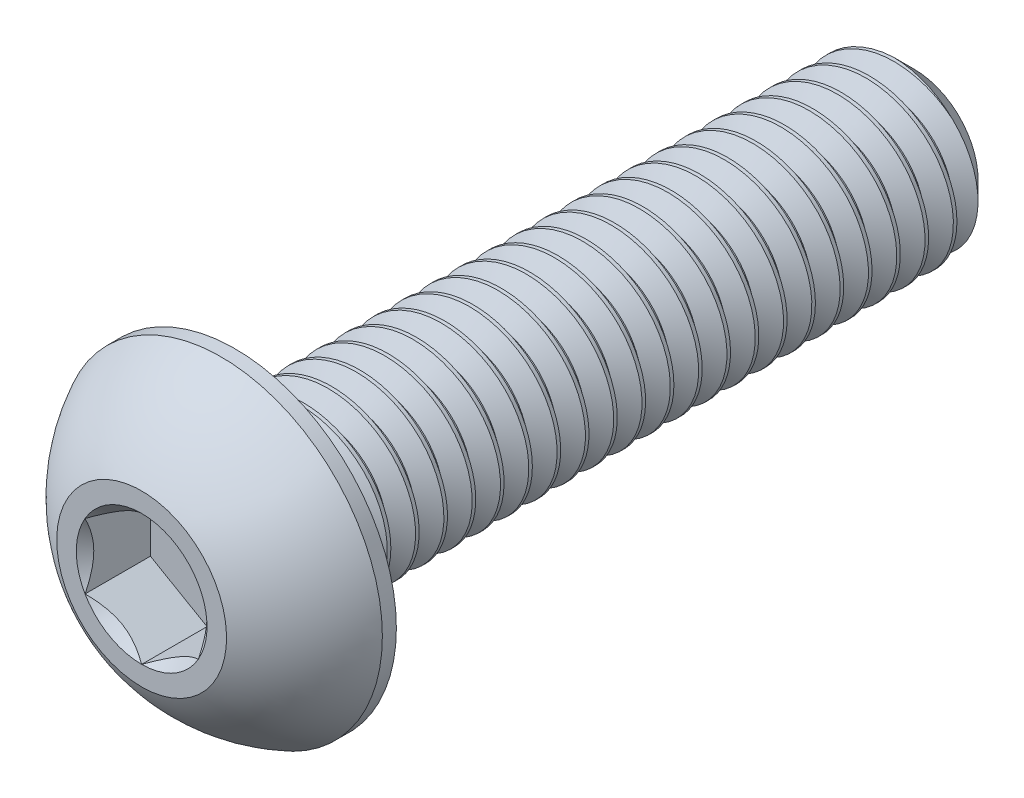
SolidWorks part; units mm, degrees
note: '?' marks a value the reader was unsure of.
ref_plane "Front" through (0, 0, 0) normal (0, 0, 1) x (1, 0, 0)
ref_plane "Top" through (0, 0, 0) normal (0, 1, 0) x (1, 0, 0)
ref_plane "Right" through (0, 0, 0) normal (1, 0, 0) x (0, 0, -1)
sketch "Sketch1" plane through (0, 0, 0) normal (1, 0, 0) x (0, 0, -1)
  line L2 (1.65, 1.5) -> (13.65, 1.5)
  line L3 (13.65, 1.5) -> (13.65, 0)
  line L4 (13.65, 0) -> (1.65, 0)
  line L6 (1.4025, 2.85) -> (1.65, 2.85) construction
  line L7 (13.65, 1.5) -> (13.65, -1.5) construction
  line L8 (0, 0) -> (1.65, 0) construction
  line L9 (1.65, 2.85) -> (1.65, -2.85) construction
  line L11 (1.65, 1.5) -> (1.65, 0)
  line L13 (0, 1) -> (0, -1) construction
  line L14 (0, 1) -> (0, 1.5) construction
  arc A3 (0, 1.5) -> (1.4025, 2.85) centre (2.7948, 0) cw construction
  dimension "D1" = 0.2475
  dimension "Head Ht" = 1.65
  dimension "Head Dia" = 5.7
  dimension "Dia" = 3
  dimension "Lg" = 12
  dimension "Hex" = 2
revolve "Revolve1" add sketch "Sketch1" angle 360 mid plane about L4
sketch "Sketch3" plane through (0, 0, -13.65) normal (0, 0, -1) x (-1, 0, 0)
  circle A0 centre (0, 0) radius 1.5
curve "Helix/Spiral1" pitch 0.5 height 12.5 turns 25
chamfer "Chamfer1" distance 0.375 angle 45 1 edges at (0, 1.5, -13.65)
sketch "Sketch7" plane through (0, 0, 0) normal (1, 0, 0) x (0, 0, -1)
  line L6 (1.4025, 2.85) -> (1.65, 2.85) construction
  line L8 (0, 0) -> (1.65, 0) construction
  line L11 (1.65, 2.85) -> (1.65, -2.85) construction
  line L12 (1.4025, 2.85) -> (1.65, 2.85)
  line L13 (0, 0) -> (1.65, 0)
  line L14 (0, 1) -> (0, -1) construction
  line L15 (1.65, 2.85) -> (1.65, 0)
  line L16 (0, 1.5) -> (0, 0)
  arc A2 (1.4025, 2.85) -> (0, 1.5) centre (2.7948, 0) ccw construction
  arc A3 (1.4025, 2.85) -> (0, 1.5) centre (2.7948, 0) ccw
revolve "Revolve2" add sketch "Sketch7" angle 360 mid plane about L13
sketch "Sketch5" plane through (0, 0, 0) normal (0, 0, 1) x (1, 0, 0)
  line L1 (1, -0.5774) -> (1, 0.5774)
  line L2 (1, 0.5774) -> (0, 1.1547)
  line L3 (0, 1.1547) -> (-1, 0.5774)
  line L4 (-1, 0.5774) -> (-1, -0.5774)
  line L5 (-1, -0.5774) -> (0, -1.1547)
  line L6 (0, -1.1547) -> (1, -0.5774)
  circle A0 centre (0, 0) radius 1 construction
extrude "Cut-Extrude2" cut sketch "Sketch5" against normal blind 1.155
sketch "Sketch6" plane through (0, 0, 0) normal (0, 0, 1) x (1, 0, 0)
  circle A0 centre (0, 0) radius 1.1547
extrude "Cut-Extrude3" cut sketch "Sketch6" against normal blind 1.155 draft 45
sketch "Sketch2" plane through (0, 0, 0) normal (1, 0, 0) x (0, 0, -1)
  line L0 (13.275, 1.5) -> (13.7125, 1.5)
  line L1 (13.7125, 1.5) -> (13.525, 1.1752)
  line L2 (13.525, 1.1752) -> (13.4625, 1.1752)
  line L3 (13.4625, 1.1752) -> (13.275, 1.5)
  line L4 (13.3688, 1.3376) -> (13.6188, 1.3376) construction
  dimension "D1" = 60
  dimension "D2" = 0.0625
  dimension "D3" = 0.25
sweep "Cut-Sweep1" cut profiles "Sketch2" path "Helix/Spiral1"
sketch "Sketch10" plane through (0, 0, 0) normal (1, 0, 0) x (0, 0, -1)
  line L0 (13.65, 1.5) -> (13.65, -1.5) construction
  point P0 (12.9, -1.5)
  dimension "D1" = 0.75
ref_axis "Center Axis 1" through (0, 0, -8.1113) along (0, 0, 1)?
ref_plane "Contact Plane 1" through (0, 0, -1.65) normal (0, 0, -1) x (-1, 0, 0)
ref_plane "Contact Plane 2" through (0, 0, 0) normal (0, 0, 1) x (1, 0, 0)
equation "\"D3@Helix/Spiral1\" = \"Lg@Sketch1\" + \"D4@Helix/Spiral1\""
equation "\"D2@Sketch2\" = \"D4@Helix/Spiral1\" * .125"
equation "\"D3@Sketch2\" = \"D4@Helix/Spiral1\" * .5"
equation "\"D1@Chamfer1\" = \"D4@Helix/Spiral1\" * .75"
equation "\"D1@Cut-Extrude2\" = \"Head Ht@Sketch1\" * .7"
equation "\"D1@Sketch1\" = \"Head Ht@Sketch1\" * .15"
equation "\"D1@Sketch10\" = \"D4@Helix/Spiral1\" * 1.5"
equation "\"D1@Cut-Extrude3\" = \"D1@Cut-Extrude2\""
